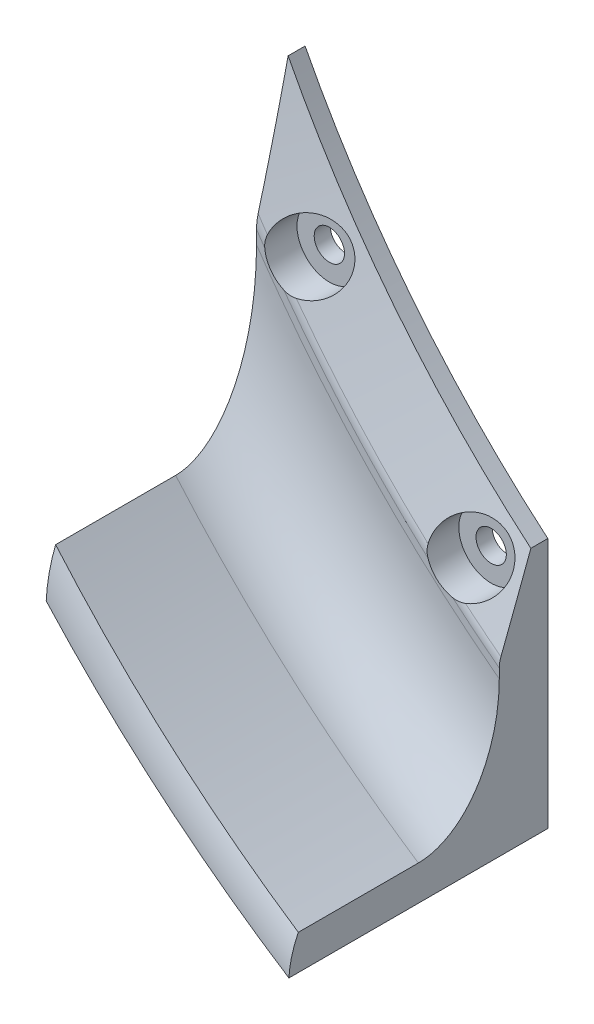
SolidWorks part; units mm, degrees
material "6061 Alloy"
ref_plane "Front Plane" through (0, 0, 0) normal (0, 0, 1) x (1, 0, 0)
ref_plane "Top Plane" through (0, 0, 0) normal (0, 1, 0) x (1, 0, 0)
ref_plane "Right Plane" through (0, 0, 0) normal (1, 0, 0) x (0, 0, -1)
sketch "Sketch1" plane through (0, 0, 0) normal (0, 0, 1) x (1, 0, 0)
  line L1 (-140.9655, 145.0225) -> (-102.8655, 145.0225)
  line L2 (-140.9655, 145.0225) -> (-140.9655, -145.0225)
  line L3 (-140.9655, -145.0225) -> (-102.8655, -145.0225)
  line L4 (-102.8655, 145.0225) -> (-102.8655, -145.0225)
  line L5 (-140.9655, 145.0225) -> (-102.8655, -145.0225) construction
  line L6 (-140.9655, -145.0225) -> (-102.8655, 145.0225) construction
  line L7 (-140.9655, 31.75) -> (140.9655, 31.75)
  line L8 (-140.9655, 31.75) -> (-140.9655, -31.75)
  line L9 (-140.9655, -31.75) -> (140.9655, -31.75)
  line L10 (140.9655, 31.75) -> (140.9655, -31.75)
  line L11 (-140.9655, 31.75) -> (140.9655, -31.75) construction
  line L12 (-140.9655, -31.75) -> (140.9655, 31.75) construction
  line L13 (102.8655, 145.0225) -> (140.9655, 145.0225)
  line L14 (102.8655, 145.0225) -> (102.8655, -145.0225)
  line L15 (102.8655, -145.0225) -> (140.9655, -145.0225)
  line L16 (140.9655, 145.0225) -> (140.9655, -145.0225)
  line L17 (102.8655, 145.0225) -> (140.9655, -145.0225) construction
  line L18 (102.8655, -145.0225) -> (140.9655, 145.0225) construction
  line L19 (-140.9655, -31.75) -> (140.9655, -31.75)
  line L20 (-140.9655, -31.75) -> (-140.9655, -69.85)
  line L21 (-140.9655, -69.85) -> (140.9655, -69.85)
  line L22 (140.9655, -31.75) -> (140.9655, -69.85)
  circle A0 centre (0, 0) radius 177.8
  circle A7 centre (0, -38.1) radius 25.4 construction
  circle A8 centre (-25.4, -38.1) radius 2.3813
  circle A9 centre (25.4, -38.1) radius 2.3813
  circle A10 centre (0, -38.1) radius 2.3812
  point P3 (-121.9155, 0)
  point P12 (121.9155, 0)
  dimension "D1" = 355.6
  dimension "D5" = 50.8
  dimension "D6" = 38.1
  dimension "D7" = 281.9311
  dimension "D10" = 4.7625
  dimension "D8" = 4.7625
  dimension "D9" = 4.7625
  dimension "D2" = 38.1
  dimension "D3" = 38.1
  dimension "D4" = 63.5
  dimension "D12" = 38.1
extrude "Boss-Extrude1" add sketch "Sketch1" along normal blind 3.175 contours L4 A0 L2 L7 | L2 L9 L4 L7 | L14 L7 L4 L9 A8 | L2 A0 L4 L9 | L16 A0 L14 L7 | L7 L14 L9 L10 | L14 A0 L16 L9 | L19 A10 L9 L4 L21 L14 A9 A8 | L2 L21 L4 L9 | L14 L21 L16 L9 region at (-120.723, 80.7079, 0) region at (0, 0, 0) region at (-121.9155, 0, 0) region at (120.723, 80.7079, 0) region at (-119.9486, -100.1295, 0) region at (0, -50.8872, 0) region at (-121.9155, -50.8, 0) region at (121.9155, 0, 0) region at (121.9155, -50.8, 0) region at (119.9486, -100.1295, 0)
sketch "Sketch2" plane through (0, 0, 3.175) normal (0, 0, 1) x (1, 0, 0)
  line L0 (-140.9655, -103.066) -> (-140.9655, -108.3585)
  line L1 (-140.9655, 108.3585) -> (-140.9655, -108.3585) construction
  line L2 (-102.8655, -141.1119) -> (-102.8655, -145.0225)
  line L3 (102.8655, -141.1119) -> (102.8655, -145.0225)
  line L4 (102.8655, -69.85) -> (102.8655, -145.0225) construction
  line L5 (140.9655, -103.066) -> (140.9655, -108.3585)
  line L6 (140.9655, 108.3585) -> (140.9655, -108.3585) construction
  line L7 (-102.8655, -69.85) -> (-102.8655, -145.0225) construction
  circle A0 centre (0, 0) radius 177.8
  circle A1 centre (0, 0) radius 174.625
  line M3 (-140.9655, 108.3585) -> (-140.9655, -108.3585)
  arc M4 (-140.9655, -108.3585) -> (-102.8655, -145.0225) centre (0, 0) ccw
  line M5 (-102.8655, -145.0225) -> (-102.8655, -69.85)
  line M7 (102.8655, -69.85) -> (102.8655, -145.0225)
  arc M8 (102.8655, -145.0225) -> (140.9655, -108.3585) centre (0, 0) ccw
  line M9 (140.9655, -108.3585) -> (140.9655, 108.3585)
  dimension "D1" = 355.6
  dimension "D2" = 349.25
extrude "Boss-Extrude2" add sketch "Sketch2" along normal blind 50.8 contours A1 M3 M4 M5 | A1 M7 M8 M9 region at (-122.8631, -125.3578, 3.175) region at (122.8631, -125.3578, 3.175)
sketch "Sketch3" plane through (0, 0, 3.175) normal (0, 0, 1) x (1, 0, 0)
  circle A0 centre (0, 0) radius 174.625
  circle A1 centre (0, 0) radius 203.8293
  dimension "D1" = 349.25
extrude "Cut-Extrude1" cut sketch "Sketch3" along normal through all and the other way through all
sketch "Sketch5" plane through (0, 0, 3.175) normal (0, 0, 1) x (1, 0, 0)
  line L0 (0, 165.1) -> (0, -165.1) construction
  line L1 (102.8655, -69.85) -> (102.8655, -141.1119) construction
  circle A0 centre (0, 0) radius 165.1 construction
  circle A1 centre (134.6155, -95.5859) radius 2.3813
  circle A2 centre (109.2155, -123.8143) radius 2.3813
  circle A3 centre (-134.6155, -95.5859) radius 2.3813
  circle A4 centre (-109.2155, -123.8143) radius 2.3813
  arc A5 (140.9655, 103.066) -> (102.8655, 141.1119) centre (0, 0) ccw construction
  dimension "D1" = 330.2
  dimension "D3" = 4.7625
  dimension "D4" = 4.7625
  dimension "D2" = 25.4
  dimension "D5" = 6.35
extrude "Cut-Extrude3" cut sketch "Sketch5" against normal through all
sketch "Sketch6" plane through (0, 0, 3.175) normal (0, 0, 1) x (1, 0, 0)
  line L0 (-102.8655, 141.1119) -> (-102.8655, 31.75) construction
  line L1 (-102.8655, 90.3119) -> (102.8655, 90.3119)
  line L2 (-102.8655, 90.3119) -> (-102.8655, 64.9119)
  line L3 (-102.8655, 64.9119) -> (102.8655, 64.9119)
  line L4 (102.8655, 90.3119) -> (102.8655, 64.9119)
  line L5 (102.8655, 141.1119) -> (102.8655, 31.75) construction
  dimension "D1" = 25.4
  dimension "D2" = 50.8
extrude "Boss-Extrude3" add sketch "Sketch6" against normal blind 3.175
sketch "Sketch7" plane through (0, 0, 3.175) normal (0, 0, 1) x (1, 0, 0)
  line L0 (102.8655, 90.3119) -> (-102.8655, 90.3119) construction
  line L1 (-157.8266, 90.3119) -> (153.0605, 90.3119)
  line L2 (-157.8266, 90.3119) -> (-157.8266, 162.3702)
  line L3 (-157.8266, 162.3702) -> (153.0605, 162.3702)
  line L4 (153.0605, 90.3119) -> (153.0605, 162.3702)
extrude "Cut-Extrude4" [suppressed] cut sketch "Sketch7" against normal through all
sketch "Sketch8" plane through (0, 0, 3.175) normal (0, 0, 1) x (1, 0, 0)
  circle A0 centre (0, -38.1) radius 38.1 construction
  circle A1 centre (-38.1, -38.1) radius 2.3812
  circle A2 centre (0, -38.1) radius 50.8 construction
  circle A3 centre (-50.8, -38.1) radius 2.3812
  circle A4 centre (0, -38.1) radius 12.7 construction
  circle A5 centre (12.7, -38.1) radius 2.3812
  circle A6 centre (-12.7, -38.1) radius 2.3812
  dimension "D1" = 76.2
  dimension "D2" = 4.7625
  dimension "D3" = 101.6
  dimension "D4" = 4.7625
  dimension "D5" = 25.4
  dimension "D6" = 4.7625
  dimension "D7" = 4.7625
extrude "Cut-Extrude5" cut sketch "Sketch8" against normal through all
sketch "Sketch9" plane through (0, 0, 3.175) normal (0, 0, 1) x (1, 0, 0)
  line L0 (102.8655, -69.85) -> (102.8655, -141.1119) construction
  line L1 (-102.8655, -69.85) -> (102.8655, -69.85)
  line L2 (-102.8655, -69.85) -> (-102.8655, -107.95)
  line L3 (-102.8655, -107.95) -> (102.8655, -107.95)
  line L4 (102.8655, -69.85) -> (102.8655, -107.95)
  dimension "D1" = 38.1
extrude "Boss-Extrude4" add sketch "Sketch9" against normal blind 3.175
sketch "Sketch10" plane through (0, 0, 3.175) normal (0, 0, 1) x (1, 0, 0)
  circle A0 centre (0, -76.2) radius 6.35
  circle A1 centre (0, -38.1) radius 2.3812 construction
  circle A2 centre (0, -76.2) radius 25.4 construction
  circle A3 centre (0, -76.2) radius 38.1 construction
  circle A4 centre (-25.4, -76.2) radius 2.3813
  circle A5 centre (-38.1, -76.2) radius 2.3812
  circle A6 centre (25.4, -76.2) radius 2.3813
  dimension "D1" = 38.1
  dimension "D2" = 12.7
  dimension "D3" = 50.8
  dimension "D4" = 76.2
  dimension "D5" = 4.7625
  dimension "D6" = 4.7625
  dimension "D7" = 4.7625
extrude "Cut-Extrude6" cut sketch "Sketch10" against normal through all
sketch "Sketch11" plane through (0, 0, 3.175) normal (0, 0, 1) x (1, 0, 0)
  line L0 (-102.8655, -107.95) -> (102.8655, -107.95) construction
  line L1 (-26.6655, -107.95) -> (26.6655, -107.95)
  line L2 (-26.6655, -107.95) -> (-26.6655, -139.7)
  line L3 (-26.6655, -139.7) -> (26.6655, -139.7)
  line L4 (26.6655, -107.95) -> (26.6655, -139.7)
  line L5 (-102.8655, -107.95) -> (-102.8655, -141.1119) construction
  line L6 (102.8655, -107.95) -> (102.8655, -141.1119) construction
  dimension "D1" = 31.75
  dimension "D2" = 76.2
  dimension "D3" = 76.2
extrude "Boss-Extrude5" add sketch "Sketch11" against normal blind 3.175
fillet "Fillet1" radius 10.16 4 edges at (26.6655, -107.95, 1.5875) (-26.6655, -107.95, 1.5875) (-26.6655, -139.7, 1.5875) (26.6655, -139.7, 1.5875)
sketch "Sketch12" plane through (0, 0, 3.175) normal (0, 0, 1) x (1, 0, 0)
  line L1 (-12.7, -63.5) -> (12.7, -63.5) construction
  line L2 (-12.7, -63.5) -> (-12.7, -88.9) construction
  line L3 (-12.7, -88.9) -> (12.7, -88.9) construction
  line L4 (12.7, -63.5) -> (12.7, -88.9) construction
  circle A0 centre (-25.4, -76.2) radius 6.35
  circle A1 centre (25.4, -76.2) radius 6.35
  circle A2 centre (0, -76.2) radius 6.35 construction
  circle A3 centre (-8.6678, -67.5323) radius 2.3812
  circle A7 centre (8.6677, -67.5322) radius 2.3813
  circle A8 centre (8.6678, -84.8677) radius 2.3812
  circle A9 centre (-8.6677, -84.8677) radius 2.3812
  point P23 (0, -76.2)
  point P24 (0, -76.2)
  dimension "D1" = 12.7
  dimension "D2" = 12.7
  dimension "D7" = 4.0323
  dimension "D9" = 4.7625
  dimension "D3" = 12.7
  dimension "D4" = 25.4
  dimension "D5" = 12.7
  dimension "D6" = 25.4
  dimension "D8" = 4.0323
  dimension "D10" = 4
extrude "Cut-Extrude7" cut sketch "Sketch12" against normal through all
fillet "Fillet2" radius 2.54 2 edges at (102.8655, 141.1119, 1.5875) (-102.8655, 141.1119, 1.5875)
sketch "Sketch13" plane through (0, 0, 3.175) normal (0, 0, 1) x (1, 0, 0)
  line L0 (-140.9655, -16.1069) -> (140.9655, -16.1069) construction
  line L1 (-140.9655, 103.066) -> (-140.9655, -103.066) construction
  line L2 (140.9655, 103.066) -> (140.9655, -103.066) construction
  text T0 "7042" font "Aero" height 25.4
extrude "Cut-Extrude8" cut sketch "Sketch13" against normal through all
sketch "Sketch14" plane through (0, 0, 3.175) normal (0, 0, 1) x (1, 0, 0)
  line L1 (-12.3972, 11.8715) -> (-9.6379, 11.8715)
  line L2 (-12.3972, 11.8715) -> (-12.3972, 3.9079)
  line L3 (-12.3972, 3.9079) -> (-9.6379, 3.9079)
  line L4 (-9.6379, 11.8715) -> (-9.6379, 3.9079)
  line L5 (-16.0587, -11.8105) -> (-13.5317, -11.8105)
  line L6 (-16.0587, -11.8105) -> (-16.0587, -17.7494)
  line L7 (-16.0587, -17.7494) -> (-13.5317, -17.7494)
  line L8 (-13.5317, -11.8105) -> (-13.5317, -17.7494)
extrude "Boss-Extrude6" add sketch "Sketch14" against normal blind 3.175
fillet "Fillet3" radius 2.54 6 edges at (-102.8655, 90.3119, 1.5875) (102.8655, 90.3119, 1.5875) (102.8655, 31.75, 1.5875) (102.8655, 64.9119, 1.5875) (-102.8655, 31.75, 1.5875) (-102.8655, 64.9119, 1.5875)
sketch "Sketch15" plane through (0, 0, 3.175) normal (0, 0, 1) x (1, 0, 0)
  line L0 (-140.9655, -30.7998) -> (-140.9655, -128.1365)
  line L1 (-140.9655, 103.066) -> (-140.9655, -103.066) construction
  line L2 (140.9655, -44.4978) -> (140.9655, -128.1365)
  line L3 (140.9655, 103.066) -> (140.9655, -103.066) construction
  line L4 (-102.8655, -107.95) -> (-102.8655, -160.34)
  line L5 (102.8655, -107.95) -> (102.8655, -160.34)
  circle A0 centre (0, 0) radius 158.75
  circle A1 centre (0, 0) radius 190.5
  circle A2 centre (-134.6155, -95.5859) radius 2.3813
  circle A3 centre (-109.2155, -123.8143) radius 2.3812
  circle A4 centre (109.2155, -123.8143) radius 2.3813
  circle A5 centre (109.2155, -123.8143) radius 2.3813 construction
  circle A6 centre (134.6155, -95.5859) radius 2.3813
  dimension "D1" = 317.5
  dimension "D2" = 381
extrude "Boss-Extrude7" add sketch "Sketch15" along normal blind 40.64 contours L0 A1 L4 A0 | L5 A1 L2 A0 region at (-122.9806, -122.07, 3.175) region at (122.9806, -122.07, 3.175)
sketch "Sketch16" plane through (0, 0, 3.175) normal (0, 0, 1) x (1, 0, 0)
  line L1 (-160.8587, 42.3801) -> (207.6811, 42.3801)
  line L2 (-160.8587, 42.3801) -> (-160.8587, 189.4949)
  line L3 (-160.8587, 189.4949) -> (207.6811, 189.4949)
  line L4 (207.6811, 42.3801) -> (207.6811, 189.4949)
  circle A0 centre (0, 0) radius 227.7547
extrude "Cut-Extrude9" cut sketch "Sketch16" against normal through all contours L1 A0 | L1 A0 | A0 L1 L4 L3 L2 region at (15.0013, 112.5626, 3.175) region at (-7.1756, -66.5524, 3.175)
sketch "Sketch17" plane through (0, 0, 43.815) normal (0, 0, 1) x (1, 0, 0)
  circle A0 centre (124.015, -121.333) radius 87.1955
extrude "Cut-Extrude10" cut sketch "Sketch17" against normal through all
chamfer "Chamfer1" distance 27.94 angle 48 1 edges at (-124.2463, -98.8151, 43.815) first distance on face at (-106.8343, -123.8143, 43.815)
sketch "Sketch18" plane through (0, 0, 3.175) normal (0, 0, -1) x (-1, 0, 0)
  circle A0 centre (0, 0) radius 171.45 construction
  circle A2 centre (134.6155, -95.5859) radius 5.08
  circle A6 centre (109.2155, -123.8143) radius 5.08
  circle A7 centre (109.2155, -123.8143) radius 2.3813 construction
  dimension "D1" = 342.9
  dimension "D2" = 10.16
  dimension "D3" = 10.16
extrude "Cut-Extrude12" cut sketch "Sketch18" against normal blind 33.02 from offset 2.54 offset against normal yes
fillet "Fillet4" radius 10.16 1 edges at (-123.0536, -140.3958, 43.815)
sketch "Sketch20" plane through (0, 0, 3.175) normal (0, 0, -1) x (-1, 0, 0)
  circle A0 centre (0, 0) radius 185.9169
  arc A1 (102.8655, -120.9142) -> (140.9655, -73.0088) centre (0, 0) ccw construction
extrude "Cut-Extrude13" cut sketch "Sketch20" against normal through all from offset 7.62 offset against normal yes
fillet "Fillet5" radius 15.24 1 edges at (-123.071, -139.3507, 10.795) second distance 12.7 first distance on face at (-114.2955, -123.8143, 10.795)
chamfer "Chamfer2" distance 10.16 angle 26 1 edges at (-124.2463, -98.8151, 10.795) first distance on face at (-114.2955, -123.8143, 10.795)
fillet "Fillet6" radius 2.54 3 edges at (-140.317, -94.0304, 10.795) (-106.0455, -131.4722, 10.795) (-125.5621, -112.9812, 10.795)
